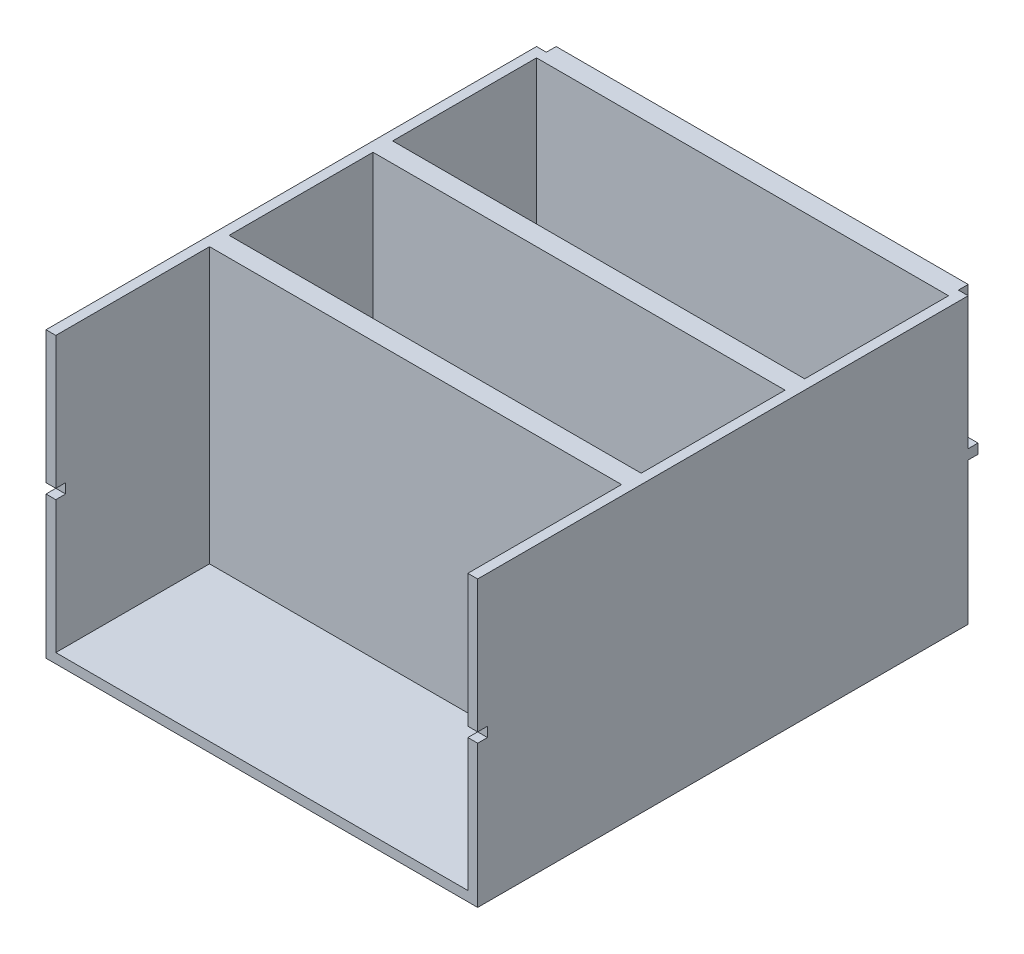
SolidWorks part; units mm, degrees
ref_plane "Front Plane" through (0, 0, 0) normal (0, 0, 1) x (1, 0, 0)
ref_plane "Top Plane" through (0, 0, 0) normal (0, 1, 0) x (1, 0, 0)
ref_plane "Right Plane" through (0, 0, 0) normal (1, 0, 0) x (0, 0, -1)
sketch "Sketch1" plane through (0, 0, 0) normal (0, 1, 0) x (1, 0, 0)
  line L1 (-110, -125) -> (110, -125)
  line L2 (-110, -125) -> (-110, 125)
  line L3 (-110, 125) -> (110, 125)
  line L4 (110, -125) -> (110, 125)
  line L5 (-110, -125) -> (110, 125) construction
  line L6 (-110, 125) -> (110, -125) construction
  point P0 (0, 0)
  dimension "D1" = 220
  dimension "D2" = 250
extrude "Boss-Extrude1" add sketch "Sketch1" along normal blind 5
sketch "Sketch2" plane through (0, 5, 0) normal (0, 1, 0) x (1, 0, 0)
  line L0 (-105, 120) -> (105, 120)
  line L1 (-110, -125) -> (110, -125)
  line L2 (-110, -125) -> (-110, 125)
  line L3 (-110, 125) -> (110, 125)
  line L4 (110, -125) -> (110, 125)
  line L5 (-110, -125) -> (110, -125) construction
  line L6 (-110, 125) -> (-110, -125) construction
  line L7 (105, -120) -> (105, -46.6667)
  line L8 (-105, -120) -> (105, -120)
  line L9 (-105, -120) -> (-105, -46.6667)
  line L10 (-105, 46.6667) -> (105, 46.6667)
  line L11 (105, 36.6667) -> (-105, 36.6667)
  line L12 (-105, 0) -> (105, 0) construction
  line L13 (105, -36.6667) -> (-105, -36.6667)
  line L14 (-105, -46.6667) -> (105, -46.6667)
  line L15 (-105, 46.6667) -> (-105, 120)
  line L16 (-105, -36.6667) -> (-105, 36.6667)
  line L17 (-105, -120) -> (-105, 120) construction
  line L18 (105, -36.6667) -> (105, 36.6667)
  line L19 (105, 46.6667) -> (105, 120)
  line L20 (105, -120) -> (105, 120) construction
  point P0 (0, 0)
  line M2 (110, -125) -> (110, 125)
  line M3 (110, 125) -> (-110, 125)
  line M4 (-110, 125) -> (-110, -125)
  line M5 (-110, -125) -> (110, -125)
  dimension "D2" = 10
  dimension "D1" = 5
extrude "Boss-Extrude2" add sketch "Sketch2" along normal blind 140 contours L18 L13 L16 L11 L9 L14 L7 L8 L19 L10 L15 M5 M2 M3 M4 region at (-106.6698, 5, 0)
sketch "Sketch3" plane through (0, 0, 125) normal (0, 0, 1) x (1, 0, 0)
  line L0 (-105, 77.5) -> (-110, 77.5)
  line L1 (-110, 77.5) -> (-110, 72.5)
  line L2 (-105, 75) -> (105, 75) construction
  line L3 (-105, 72.5) -> (-110, 72.5)
  line L4 (-105, 145) -> (-105, 5)
  line L5 (-105, 5) -> (105, 5)
  line L6 (105, 5) -> (105, 145)
  line L7 (0, 145) -> (0, 0) construction
  line L8 (-110, 0) -> (110, 0)
  line L9 (110, 0) -> (110, 145)
  line L10 (110, 145) -> (-110, 145)
  line L11 (-110, 145) -> (-110, 0)
  line L12 (-110, 0) -> (110, 0) construction
  line L13 (110, 0) -> (110, 145) construction
  line L15 (-110, 145) -> (-110, 0) construction
  line L17 (110, 145) -> (-110, 145)
  line L18 (105, 72.5) -> (110, 72.5)
  line L19 (105, 77.5) -> (110, 77.5)
  line L20 (110, 77.5) -> (110, 72.5)
  line M6 (110, 0) -> (110, 145)
  line M8 (-110, 145) -> (-110, 0)
  line M10 (110, 145) -> (-110, 145)
  dimension "D3" = 5
  dimension "D1" = 0
  dimension "D2" = 5
extrude "Cut-Extrude1" cut sketch "Sketch3" against normal up to surface (5 mm away) contours L5 L6 L4 M10 | L19 L6 L18 M6 | L4 L0 L3 M8 region at (-107.5, 75, 125) region at (0, 75, 125) region at (107.5, 75, 125) up to face at (0, 75, 120)
sketch "Sketch4" plane through (0, 0, -120) normal (0, 0, 1) x (1, 0, 0)
  line L0 (-105, 145) -> (-105, 5)
  line L1 (-105, 5) -> (105, 5)
  line L2 (105, 5) -> (105, 145)
  line L3 (105, 145) -> (-105, 145)
  line L6 (105, 77.5) -> (110, 77.5)
  line L7 (110, 77.5) -> (110, 72.5)
  line L8 (110, 72.5) -> (105, 72.5)
  line L9 (-105, 77.5) -> (-110, 77.5)
  line L10 (-110, 77.5) -> (-110, 72.5)
  line L11 (-110, 72.5) -> (-105, 72.5)
  line M1 (-105, 5) -> (105, 5)
  line M2 (105, 5) -> (105, 145)
  line M3 (105, 145) -> (-105, 145)
  line M4 (-105, 145) -> (-105, 5)
extrude "Boss-Extrude3" add sketch "Sketch4" against normal blind 5 from surface contours M2 M3 M4 M1 | L10 L11 L0 L9 | L8 L7 L6 L2 region at (0, 75, -120) region at (-107.5, 75, -120) region at (107.5, 75, -120) starting at face at (0, 72.5, -125)
